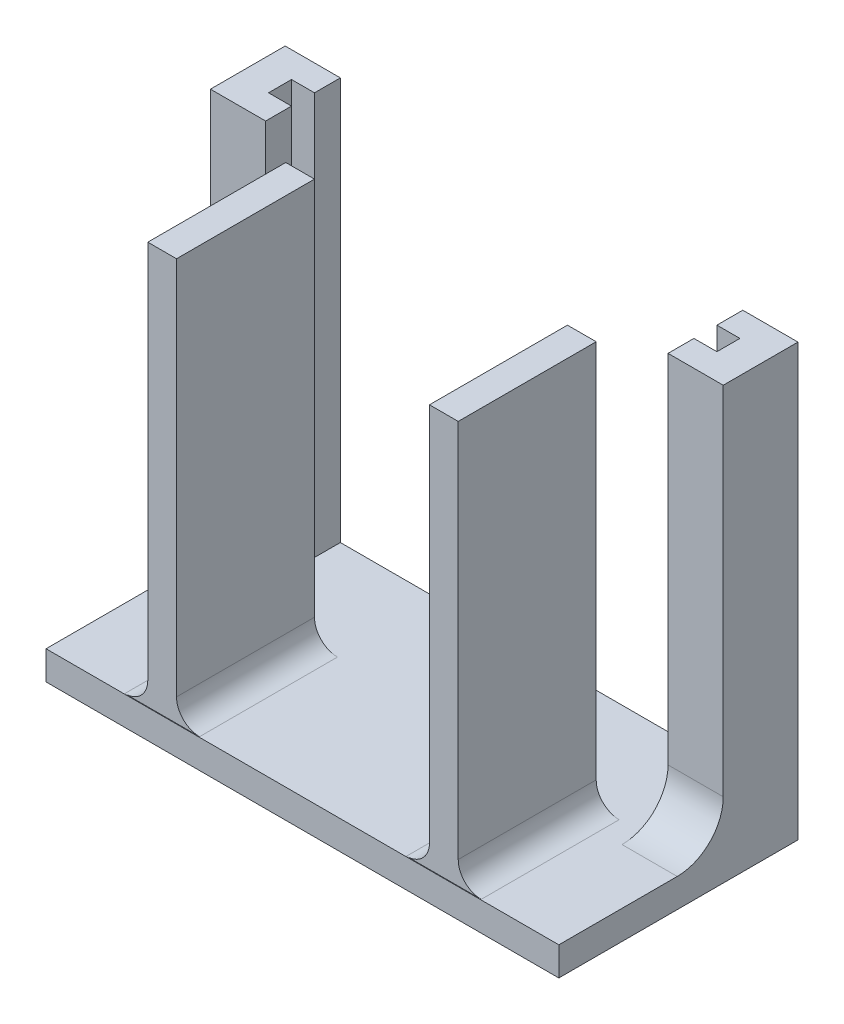
SolidWorks part; units mm, degrees
ref_plane "Front Plane" through (0, 0, 0) normal (0, 0, 1) x (1, 0, 0)
ref_plane "Top Plane" through (0, 0, 0) normal (0, 1, 0) x (1, 0, 0)
ref_plane "Right Plane" through (0, 0, 0) normal (1, 0, 0) x (0, 0, -1)
ref_plane "Plane1" through (0, -19, 0) normal (0, 1, 0) x (1, 0, 0)
sketch "Sketch1" plane through (0, -19, 0) normal (0, 1, 0) x (1, 0, 0)
  line L0 (0, 0) -> (0, -21.3085) construction
  line L1 (-19.5, 0.5) -> (-17.5, 0.5)
  line L2 (-17.5, 0.5) -> (-17.5, 2.75)
  line L3 (-17.5, 2.75) -> (-22.3, 2.75)
  line L4 (-22.3, 2.75) -> (-22.3, -3.75)
  line L5 (-22.3, -3.75) -> (-17.5, -3.75)
  line L6 (-17.5, -3.75) -> (-17.5, -1.5)
  line L7 (-17.5, -1.5) -> (-19.5, -1.5)
  line L8 (-19.5, -1.5) -> (-19.5, 0.5)
  line L10 (19.5, -1.5) -> (19.5, 0.5)
  line L11 (17.5, -1.5) -> (19.5, -1.5)
  line L12 (17.5, -3.75) -> (17.5, -1.5)
  line L13 (22.3, -3.75) -> (17.5, -3.75)
  line L14 (22.3, 2.75) -> (22.3, -3.75)
  line L15 (17.5, 2.75) -> (22.3, 2.75)
  line L16 (17.5, 0.5) -> (17.5, 2.75)
  line L17 (19.5, 0.5) -> (17.5, 0.5)
  line L18 (11, -6) -> (11, -18)
  line L19 (-13.5, -6) -> (-11, -6)
  line L20 (-13.5, -6) -> (-13.5, -18)
  line L21 (-13.5, -18) -> (-11, -18)
  line L22 (-11, -6) -> (-11, -18)
  line L23 (13.5, -18) -> (11, -18)
  line L24 (13.5, -6) -> (13.5, -18)
  line L25 (13.5, -6) -> (11, -6)
  dimension "D1" = 2
  dimension "D2" = 17.5
  dimension "D3" = 4.8
  dimension "D4" = 2.25
  dimension "D5" = 0.5
  dimension "D6" = 2
  dimension "D7" = 6.5
  dimension "D8" = 12
  dimension "D9" = 6
  dimension "D10" = 2.5
  dimension "D11" = 11
extrude "Boss-Extrude1" add sketch "Sketch1" along normal blind 35
sketch "Sketch2" plane through (0, -19, 0) normal (0, 1, 0) x (1, 0, 0)
  line L1 (-22.3, 2.75) -> (22.3, 2.75)
  line L2 (-22.3, 2.75) -> (-22.3, -18.05)
  line L3 (-22.3, -18.05) -> (22.3, -18.05)
  line L4 (22.3, 2.75) -> (22.3, -18.05)
  dimension "D1" = 44.6
  dimension "D2" = 20.8
extrude "Boss-Extrude2" add sketch "Sketch2" against normal blind 2.5
fillet "Fillet1" radius 2 4 edges at (-13.5, -19, 12) (11, -19, 12) (-11, -19, 12) (13.5, -19, 12)
fillet "Fillet2" radius 4 2 edges at (19.9, -19, 3.75) (-19.9, -19, 3.75)
